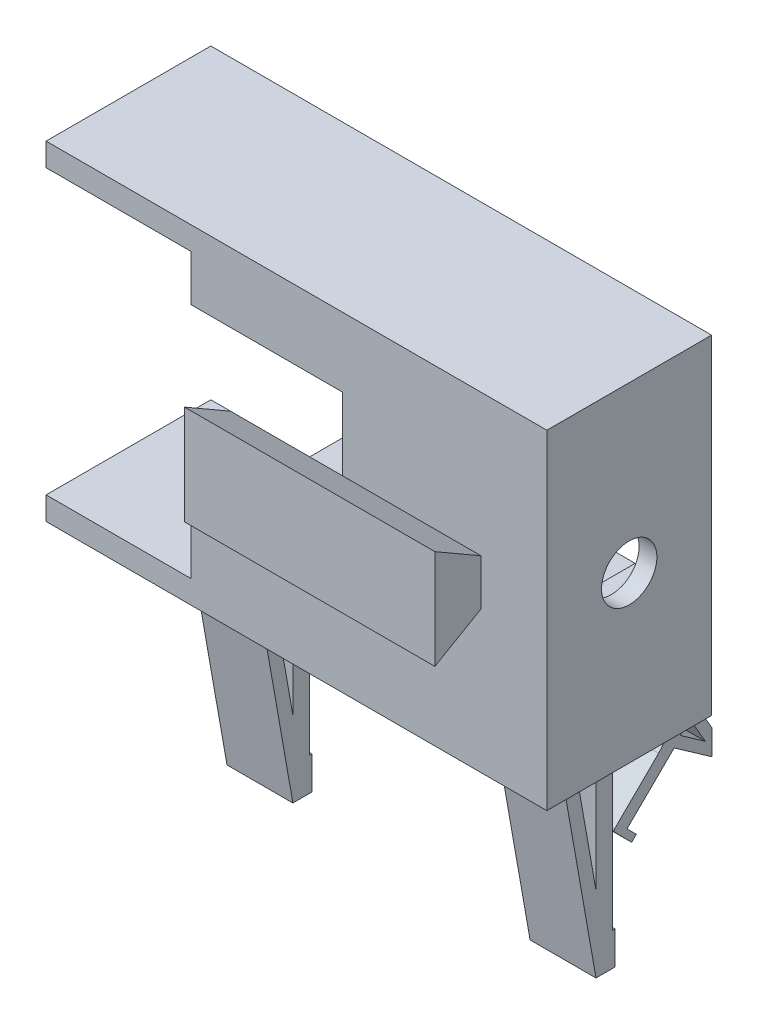
SolidWorks part; units mm, degrees
ref_plane "Front Plane" through (0, 0, 0) normal (0, 0, 1) x (1, 0, 0)
ref_plane "Top Plane" through (0, 0, 0) normal (0, 1, 0) x (1, 0, 0)
ref_plane "Right Plane" through (0, 0, 0) normal (1, 0, 0) x (0, 0, -1)
sketch "Sketch1" plane through (0, 0, 0) normal (0, 0, 1) x (1, 0, 0)
  line L0 (0, 25) -> (-38, 25)
  line L1 (-38, 25) -> (-38, -25)
  line L2 (-38, -25) -> (0, -25)
  line L3 (0, 25) -> (0, -25)
  point P3 (-38, 0)
  dimension "D1" = 38
  dimension "D2" = 50
extrude "Boss-Extrude1" add sketch "Sketch1" along normal blind 25
ref_plane "Plane2" through (-28, 0, 0) normal (-1, 0, 0) x (0, 0, 1)
sketch "Sketch11" plane through (-28, 0, 0) normal (1, 0, 0) x (0, 0, -1)
  line L3 (-5.0442, -29.7762) -> (-5.0442, -55.7262)
  line L8 (-5.0442, -55.7262) -> (-4.6442, -55.7262)
  line L11 (-4.6442, -55.7262) -> (-4.6442, -60.7262)
  line L18 (-5.0442, -29.7762) -> (-4.5442, -29.7762)
  line L21 (10.0487, -36.6379) -> (5.3792, -28.55)
  line L22 (-4.6442, -60.7262) -> (-6.5442, -60.7262)
  line L23 (-6.5442, -31.3957) -> (-6.5442, -25)
  line L24 (-6.5442, -60.7262) -> (-6.5442, -31.3957)
  line L32 (4.3146, -36.4275) -> (-2.8278, -43.4728)
  line L33 (-2.8278, -43.4728) -> (-1.4233, -44.8967)
  line L34 (-1.4233, -44.8967) -> (-2.1352, -45.599)
  line L35 (-2.1352, -45.599) -> (-4.9442, -42.7512)
  line L36 (-4.9442, -42.7512) -> (1.967, -35.934)
  line L37 (-25, -25) -> (0, -25) construction
  line L38 (-4.5442, -29.7762) -> (-4.5442, -28.4534)
  line L39 (-0.5, -25.3048) -> (-0.5, -25)
  line L40 (-0.5, -25) -> (0, -25)
  line L41 (0, -25) -> (0, -25.3048)
  line L42 (9.0539, -37.9149) -> (6.1568, -32.8969)
  line L44 (-7.5442, -49.2087) -> (-11.8129, -25)
  line L45 (9.0539, -37.9149) -> (5.2556, -35.2552)
  line L47 (4.3146, -36.4275) -> (10.0487, -40.4426)
  line L48 (10.0487, -40.4426) -> (10.0487, -36.6379)
  line L49 (-11.8129, -25) -> (-13.8437, -25)
  line L50 (-13.8437, -25) -> (-7.5442, -60.7262)
  line L51 (-6.5442, -25) -> (-7.5442, -25)
  line L52 (-7.5442, -25) -> (-7.5442, -60.7262)
  line L53 (-7.5442, -60.7262) -> (-6.5442, -60.7262)
  arc A0 (-4.0749, -26.5445) -> (4.3146, -36.4275) centre (-0.25, -31.8) cw
  arc A1 (1.967, -35.934) -> (-4.0442, -28.0442) centre (-1.5442, -32.3743) ccw
  arc A2 (-5.0442, -29.7762) -> (-4.0442, -28.0442) centre (-3.0442, -29.7762) cw
  arc A3 (-6.5442, -31.3957) -> (-4.0749, -26.5445) centre (-0.5442, -31.3957) cw
  point P27 (-5.0442, -42.7512)
  point P32 (-0.25, -25)
  dimension "D8" = 2
  dimension "D9" = 6.5
  dimension "D10" = 2
  dimension "D3" = 5
  dimension "D11" = 2
  dimension "D2" = 6.8
  dimension "D12" = 6
  dimension "D14" = 25.95
  dimension "D22" = 1.5
  dimension "D1" = 1
  dimension "D4" = 5
  dimension "D5" = 0.4
  dimension "D6" = 0.1
  dimension "D7" = 2
  dimension "D13" = 1.5
  dimension "D15" = 0.5
  dimension "D16" = 0.5
  dimension "D17" = 60
  dimension "D18" = 1.5
  dimension "D19" = 1.5
  dimension "D20" = 35
  dimension "D21" = 1
  dimension "D23" = 7
  dimension "D24" = 2
  dimension "D26" = 10
extrude "Boss-Extrude8" add sketch "Sketch11" along normal blind 10 contours L22 L3 | L22 L11 L8 | L24 A3 A0 L32 L33 L34 L35 L36 A1 A2 L3 L8 L11 L22 | L53 L52 L23 L24 | A0 L45 L48 L47 | A0 L39 L41 | L44 L52 L50 region at (-28, -42.7512, 4.6676) region at (-28, -42.8631, 7.0442) region at (-28, -40.1682, 10.2188) region at (-28, -25.1508, 0.25) region at (-28, -35.9513, -4.9221)
fillet "Fillet1" radius 0.3 1 edges at (-23, -42.7512, 4.9442)
mirror "Mirror1" about plane through (0, 0, 0) normal (1, 0, 0) of "Fillet1", "Boss-Extrude1", "Boss-Extrude8"
sketch "Sketch15" plane through (0, 0, 0) normal (0, 0, -1) x (-1, 0, 0)
  line L0 (38, 14.5) -> (-7, 14.5)
  line L1 (38, 25) -> (38, -25) construction
  line L2 (-7, 14.5) -> (-7, -14.5)
  line L3 (-7, -14.5) -> (38, -14.5)
  line L4 (38, 25) -> (38, -25)
  point P6 (-7, 0)
  point P7 (38, 0)
  line M8 (38, -25) -> (38, 25)
  dimension "D1" = 45
  dimension "D2" = 29
extrude "Cut-Extrude7" cut sketch "Sketch15" against normal up to next contours L2 L3 L0 M8 region at (-15.5, 0, 0)
ref_plane "Plane1" through (28, 0, 0) normal (1, 0, 0) x (0, 0, -1)
sketch "Sketch2" plane through (28, 0, 0) normal (-1, 0, 0) x (0, 0, 1)
  line L0 (25, 3.5) -> (32, 7.5415)
  line L1 (25, 25) -> (25, 14.5) construction
  line L2 (32, 7.5415) -> (32, -7.5415)
  line L3 (32, -7.5415) -> (25, -3.5)
  line L4 (25, 25) -> (25, -25) construction
  line L6 (25, 25) -> (25, -25)
  line L7 (0, 25) -> (0, -25) construction
  line L8 (0, 25) -> (0, -25)
  point P8 (32, 0)
  point P13 (0, 0)
  dimension "D5" = 7
  dimension "D1" = 60
  dimension "D2" = 60
  dimension "D3" = 7
extrude "Boss-Extrude2" add sketch "Sketch2" along normal blind 38 contours L3 L2 L0 | L0 L2 L3 region at (28, 0, 28.927)
sketch "Sketch16" plane through (7, 0, 0) normal (-1, 0, 0) x (0, 0, 1)
  line L1 (25, 14.5) -> (0, 14.5) construction
  line L2 (25, 14.5) -> (0, 14.5)
  circle A1 centre (12.5, 0) radius 11.1
  point P1 (12.5, 14.5)
  dimension "D1" = 22.2
extrude "Cut-Extrude8" cut sketch "Sketch16" against normal blind 3.5 contours A1 region at (7, 0, 12.5)
sketch "Sketch17" plane through (10.5, 0, 0) normal (-1, 0, 0) x (0, 0, 1)
  circle A2 centre (12.5, 0) radius 6.05
  circle A3 centre (12.5, 0) radius 11.1 construction
  circle A4 centre (12.5, 0) radius 11.1
  dimension "D1" = 12.1
extrude "Cut-Extrude9" cut sketch "Sketch17" against normal blind 19 contours A2 region at (10.5, 0, 12.5)
sketch "Sketch18" plane through (29.5, 0, 0) normal (-1, 0, 0) x (0, 0, 1)
  line L0 (12.5, 7.5) -> (0, 7.5)
  line L1 (0, 14.5) -> (0, -14.5) construction
  line L2 (0, 7.5) -> (0, -7.5)
  line L3 (0, -7.5) -> (12.5, -7.5)
  circle A0 centre (12.5, 0) radius 6.05 construction
  circle A1 centre (12.5, 0) radius 6.05
  circle A2 centre (12.5, 0) radius 7.5
  circle M3 centre (12.5, 0) radius 6.05
  dimension "D1" = 15
extrude "Cut-Extrude10" cut sketch "Sketch18" against normal blind 5.8 contours A2 L0 L2 L3 | A2 M3 | M3 region at (29.5, 0, 3.5167) region at (29.5, 5.1533, 17.6533) region at (29.5, 0, 12.5)
sketch "Sketch19" plane through (29.5, 0, 0) normal (1, 0, 0) x (0, 0, -1)
  line L0 (-12.5, 6.05) -> (0, 6.05)
  line L1 (0, 7.5) -> (0, -7.5) construction
  line L2 (-12.5, -6.05) -> (0, -6.05)
  line L3 (0, -6.05) -> (0, 6.05)
  circle A0 centre (-12.5, 0) radius 6.05 construction
  arc A1 (-12.5, 6.05) -> (-12.5, -6.05) centre (-12.5, 0) ccw
extrude "Cut-Extrude11" cut sketch "Sketch19" against normal blind 15.8
sketch "Sketch20" plane through (10.5, 0, 0) normal (-1, 0, 0) x (0, 0, 1)
  circle A0 centre (4.5, 0) radius 1.85
  circle A1 centre (12.5, 0) radius 6.05 construction
  circle A2 centre (12.5, 0) radius 6.05
  circle A3 centre (12.5, 0) radius 8 construction
  dimension "D1" = 3.7
  dimension "D2" = 16
extrude "Cut-Extrude12" cut sketch "Sketch20" against normal blind 19 contours A0 region at (10.5, 0, 4.5)
ref_axis "Axis1" through (29.5, 0, 12.5) along (-1, 0, 0)
pattern_circular "CirPattern1" count 2 every 90 about axis through (29.5, 0, 12.5) along (-1, 0, 0) of "Cut-Extrude12" other way count 2
sketch "Sketch24" plane through (13.7, 0, 0) normal (1, 0, 0) x (0, 0, -1)
  line L1 (-15.3, 10.8) -> (-15.3, -10.8)
  line L2 (-15.3, -10.8) -> (0, -10.8)
  line L3 (0, -10.8) -> (0, 10.8)
  line L4 (0, 10.8) -> (-15.3, 10.8)
  circle A2 centre (-12.5, -8) radius 1.85 construction
  circle A3 centre (-12.5, -8) radius 1.85
  circle A4 centre (-12.5, 8) radius 1.85 construction
  circle A5 centre (-12.5, 8) radius 1.85
  point P8 (-15.3, 0)
  dimension "D1" = 2.8
  dimension "D2" = 2.8
extrude "Cut-Extrude13" cut sketch "Sketch24" along normal blind 16
sketch "Sketch25" plane through (35.3, 0, 0) normal (-1, 0, 0) x (0, 0, 1)
  circle A0 centre (12.5, 0) radius 4.2
  dimension "D1" = 8.4
extrude "Cut-Extrude14" cut sketch "Sketch25" against normal through all
sketch "Sketch26" plane through (0, 0, 0) normal (0, 0, -1) x (-1, 0, 0)
  line L1 (-18, -29.7762) -> (-18, -55.7262) construction
  line L2 (-18, -29.7762) -> (-18, -55.7262) construction
  circle A0 centre (0, -42.7512) radius 6.5
  point P4 (-18, -42.7512)
  dimension "D1" = 13
extrude "Boss-Extrude9" [suppressed] add sketch "Sketch26" against normal blind 86 separate body
sketch "Sketch27" plane through (0, 0, 0) normal (0, 0, -1) x (-1, 0, 0)
  line L0 (38, -21.5) -> (38, 21.5)
  line L1 (38, 25) -> (38, 14.5) construction
  line L4 (16, 21.5) -> (16, -21.5)
  line L5 (16, -21.5) -> (38, -21.5)
  line L7 (16, 21.5) -> (38, 21.5)
  point P3 (16, 0)
  dimension "D2" = 22
  dimension "D3" = 43
extrude "Cut-Extrude15" cut sketch "Sketch27" against normal blind 25
equation "\"Width\"= 76mm"
equation "\"D1@Sketch1\"=\"Width\"/2"
equation "\"Height\"= 50mm"
equation "\"D2@Sketch1\"=\"Height\""
equation "\"D1@Boss-Extrude2\"=\"Width\" / 2 "
equation "\"SpringD\"= 5"
equation "\"DovetailAngle\" = 60deg"
equation "\"DovetailHeight\" = 7mm"
equation "\"DovetailBase\" = 7mm"
equation "\"D5@Sketch2\"=\"DovetailBase\""
equation "\"D1@Sketch2\"=\"DovetailAngle\""
equation "\"D2@Sketch2\"=\"DovetailAngle\""
equation "\"D3@Sketch2\"=\"DovetailHeight\""
